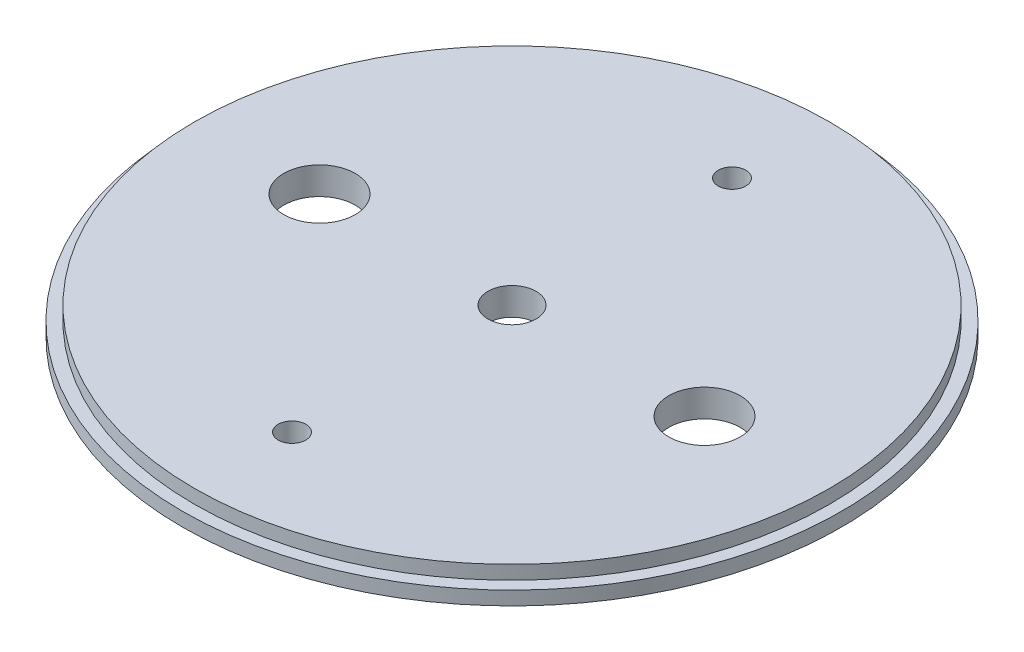
SolidWorks part; units mm, degrees
material "6061-T6 (SS)"
ref_plane "Front Plane" through (0, 0, 0) normal (0, 0, 1) x (1, 0, 0)
ref_plane "Top Plane" through (0, 0, 0) normal (0, 1, 0) x (1, 0, 0)
ref_plane "Right Plane" through (0, 0, 0) normal (1, 0, 0) x (0, 0, -1)
sketch "Sketch1" plane through (0, 0, 0) normal (0, 1, 0) x (1, 0, 0)
  circle A0 centre (0, 0) radius 73.3171
  circle A1 centre (0, 0) radius 76.0984
  dimension "D1" = 146.6342
  dimension "D2" = 152.1968
extrude "Boss-Extrude1" add sketch "Sketch1" along normal blind 3.175 contours A0 | A1 A0 region at (0, 0, 0) region at (-73.946, 0, 0)
extrude "Boss-Extrude2" add sketch "Sketch1<3>" along normal blind 6.35 contours A0 region at (0, 0, 0)
sketch "Sketch1<3>" plane through (0, 0, 0) normal (0, 1, 0) x (1, 0, 0) same geometry as "Sketch1"
sketch "Sketch3" plane through (0, 0, 0) normal (0, -1, 0) x (1, 0, 0)
  line L0 (44.45, 0) -> (-44.45, 0) construction
  line L1 (0, -50.8) -> (0, 50.8) construction
  circle A0 centre (0, 0) radius 5.5562
  circle A1 centre (-44.45, 0) radius 8.25
  circle A2 centre (44.45, 0) radius 8.25
  circle A3 centre (0, 50.8) radius 4.9609
  circle A4 centre (0, -50.8) radius 4.9609
  point P6 (0, 0)
  point P14 (0, 0)
  dimension "D1" = 11.1125
  dimension "D2" = 16.5001
  dimension "D3" = 9.9219
  dimension "D4" = 101.6
  dimension "D5" = 88.9
hole_wizard "1/4 (0.25) Diameter Hole1" positions "Sketch4" profile "Sketch5" hole size "1/4" standard "ANSI Inch" end condition through all
sketch "Sketch4" plane through (0, 0, 0) normal (0, -1, 0) x (-1, 0, 0)
  point P0 (0, 50.8)
  point P3 (0, -50.8)
sketch "Sketch5" plane through (0, 0, -50.8) normal (1, 0, 0) x (0, 0, -1)
  line L0 (0, 0) -> (0, 6.35)
  line L1 (0, 6.35) -> (3.175, 6.35)
  line L2 (3.175, 6.35) -> (3.175, 0)
  line L5 (3.175, 0) -> (0, 0)
  line L11 (0, -6.35) -> (0, 107.95) construction
  dimension "Thru Hole Dia." = 6.35
  dimension "Thru Hole Depth" = 6.35
extrude "Cut-Extrude1" [suppressed] cut sketch "Sketch3" against normal through all
hole_wizard "M18x1.5 Tapped Hole1" positions "Sketch6" profile "Sketch7" tap size "M18x1.5" standard "ANSI Metric" end condition through all
sketch "Sketch6" plane through (0, 0, 0) normal (0, -1, 0) x (-1, 0, 0)
  point P0 (44.45, 0)
  point P3 (-44.45, 0)
sketch "Sketch7" plane through (-44.45, 0, 0) normal (1, 0, 0) x (0, 0, -1)
  line L0 (0, 0) -> (0, 6.35)
  line L1 (0, 6.35) -> (8.25, 6.35)
  line L2 (8.25, 6.35) -> (8.25, 0)
  line L5 (8.25, 0) -> (0, 0)
  line L11 (0, -6.35) -> (0, 107.95) construction
  dimension "Thru Tap Drill Dia." = 16.5
  dimension "Thru Tap Drill Depth" = 6.35
cosmetic thread "Hole Thread1" parameters "D2"=18
cosmetic thread "Hole Thread2" parameters "D2"=18
extrude "Cut-Extrude2" cut sketch "Sketch3<3>" against normal through all contours A0
sketch "Sketch3<3>" plane through (0, 0, 0) normal (0, -1, 0) x (1, 0, 0) same geometry as "Sketch3"
